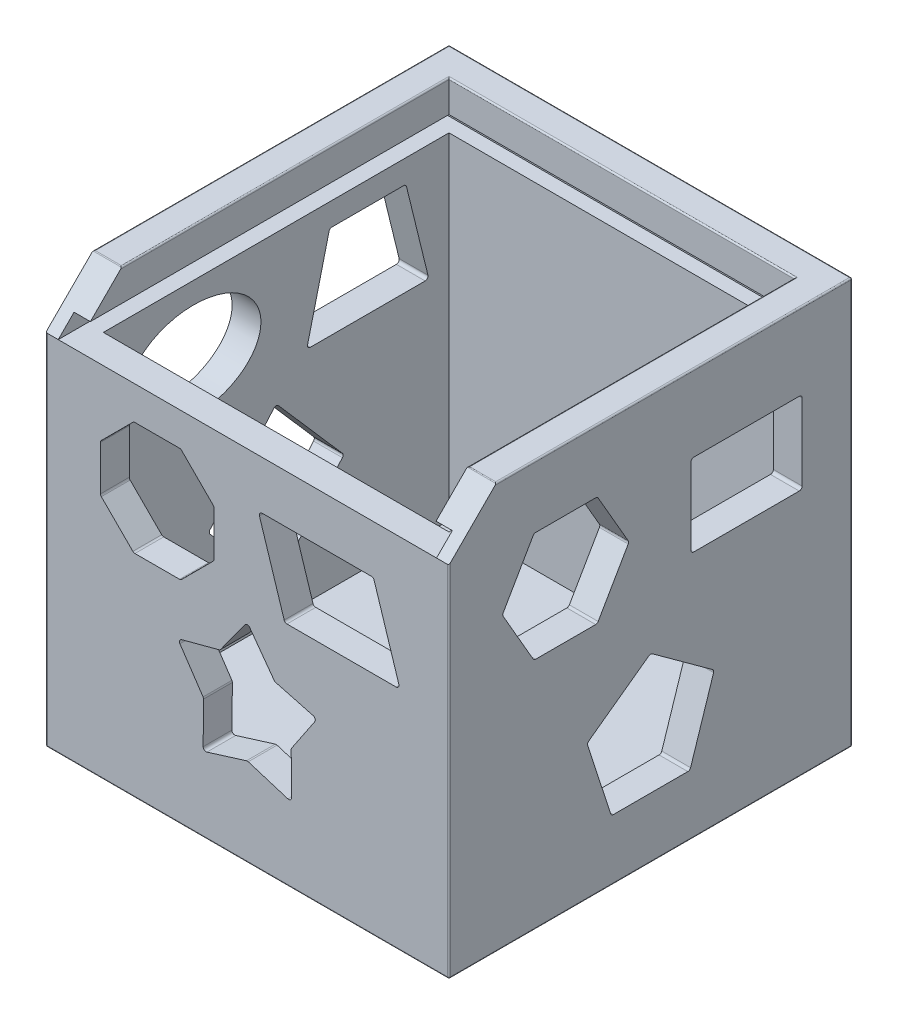
SolidWorks part; units mm, degrees
ref_plane "Front Plane" through (0, 0, 0) normal (0, 0, 1) x (1, 0, 0)
ref_plane "Top Plane" through (0, 0, 0) normal (0, 1, 0) x (1, 0, 0)
ref_plane "Right Plane" through (0, 0, 0) normal (1, 0, 0) x (0, 0, -1)
sketch "Sketch2" plane through (0, 0, 0) normal (0, 1, 0) x (1, 0, 0)
  line L0 (0, 0) -> (96.4229, 0) construction
  line L1 (-70, 70) -> (70, 70)
  line L2 (-70, 70) -> (-70, -70)
  line L3 (-70, -70) -> (70, -70)
  line L4 (70, 70) -> (70, -70)
  line L5 (0, 0) -> (0, 66.2411) construction
  dimension "D1" = 140
  dimension "D2" = 140
extrude "Boss-Extrude1" add sketch "Sketch2" along normal blind 141
sketch "Sketch3" plane through (0, 141, 0) normal (0, 1, 0) x (1, 0, 0)
  line L0 (0, 0) -> (0, 34.3646) construction
  line L1 (-60, 60) -> (60, 60)
  line L2 (-60, 60) -> (-60, -60)
  line L3 (-60, -60) -> (60, -60)
  line L4 (60, 60) -> (60, -60)
  line L5 (0, 0) -> (41.296, 0) construction
  line L6 (-70, 70) -> (-70, -70) construction
  line L7 (70, 70) -> (-70, 70) construction
  dimension "D1" = 10
  dimension "D2" = 10
extrude "Cut-Extrude1" cut sketch "Sketch3" against normal offset from surface (133 mm away) 8 up to face at (0, 0, 0)
sketch "Sketch4" plane through (0, 0, 70) normal (0, 0, 1) x (1, 0, 0)
  line L0 (0, 0) -> (0, 102.2053) construction
  line L1 (-65.6643, 130) -> (65.6643, 130)
  line L2 (-65.6643, 130) -> (-65.6643, 124.5)
  line L3 (-65.6643, 124.5) -> (65.6643, 124.5)
  line L4 (65.6643, 130) -> (65.6643, 124.5)
  line L5 (-70, 141) -> (70, 141) construction
  dimension "D1" = 11
  dimension "D2" = 5.5
extrude "Cut-Extrude2" cut sketch "Sketch4" against normal offset from surface (135 mm away) 5 up to face at (0, 70.5, -70)
sketch "Sketch5" plane through (-70, 0, 0) normal (-1, 0, 0) x (0, 0, 1)
  line L0 (53.5, 141) -> (70, 124.5)
  line L1 (-70, 141) -> (70, 141) construction
  line L2 (70, 141) -> (70, 0) construction
  line L3 (70, 124.5) -> (70, 141)
  line L4 (70, 141) -> (53.5, 141)
  dimension "D1" = 16.5
  dimension "D2" = 16.5
extrude "Cut-Extrude3" cut sketch "Sketch5" against normal through all
sketch "Sketch6" plane through (0, 0, 70) normal (0, 0, 1) x (1, 0, 0)
  line L0 (0, 0) -> (0, 54.0681) construction
  line L1 (-11.6, 85.4542) -> (-11.6, 100.9458)
  line L2 (-11.8929, 101.6529) -> (-22.8471, 112.6071)
  line L3 (-23.5542, 112.9) -> (-39.0458, 112.9)
  line L4 (-39.7529, 112.6071) -> (-50.7071, 101.6529)
  line L5 (-51, 100.9458) -> (-51, 85.4542)
  line L6 (-50.7071, 84.7471) -> (-39.7529, 73.7929)
  line L7 (-39.0458, 73.5) -> (-23.5542, 73.5)
  line L8 (-22.8471, 73.7929) -> (-11.8929, 84.7471)
  line L9 (-15.3591, 27.2492) -> (-15.2085, 41.6454)
  line L15 (0.8079, 71.1757) -> (9.2914, 59.5436)
  line L16 (14.0624, 26.2838) -> (0.2968, 30.5619)
  line L17 (-22.842, 55.7041) -> (-9.842, 59.1665)
  line L18 (23.4148, 54.1803) -> (15.3782, 42.2134)
  line L19 (-9.2914, 59.5436) -> (-0.8079, 71.1757)
  line L20 (9.842, 59.1665) -> (22.842, 55.7041)
  line L21 (-0.2968, 30.5619) -> (-14.0624, 26.2838)
  line L22 (-15.3782, 42.2134) -> (-23.4148, 54.1803)
  line L23 (15.2085, 41.6454) -> (15.3591, 27.2492)
  line L24 (0, 30.6541) -> (0, 72.2835) construction
  line L25 (0, 46.5335) -> (47.7455, 46.5335) construction
  line L26 (-24.196, 55.3435) -> (24.196, 55.3435) construction
  line L27 (-15.3734, 25.8763) -> (15.3734, 25.8763) construction
  line L28 (4.1927, 106.397) -> (12.7784, 79.397)
  line L29 (13.7314, 78.7) -> (51.6327, 78.7)
  line L30 (52.5857, 80.003) -> (44, 107.003)
  line L31 (43.047, 107.7) -> (5.1457, 107.7)
  line L32 (-70, 124.5) -> (-70, 0) construction
  line L33 (65.6643, 124.5) -> (-65.6643, 124.5) construction
  line L34 (70, 124.5) -> (70, 0) construction
  line L37 (-31.3, 93.2) -> (27.5657, 93.2) construction
  line L38 (-70, 0) -> (70, 0) construction
  circle A0 centre (-31.3, 93.2) radius 19.7 construction
  circle A1 centre (0, 46.5335) radius 15.8794 construction
  circle A2 centre (0, 46.5335) radius 25.75 construction
  arc A3 (12.7784, 79.397) -> (13.7314, 78.7) centre (13.7314, 79.7) ccw
  arc A4 (51.6327, 78.7) -> (52.5857, 80.003) centre (51.6327, 79.7) ccw
  arc A5 (44, 107.003) -> (43.047, 107.7) centre (43.047, 106.7) ccw
  arc A6 (4.1927, 106.397) -> (5.1457, 107.7) centre (5.1457, 106.7) cw
  arc A7 (-50.7071, 101.6529) -> (-51, 100.9458) centre (-50, 100.9458) ccw
  arc A8 (-51, 85.4542) -> (-50.7071, 84.7471) centre (-50, 85.4542) ccw
  arc A9 (-39.7529, 73.7929) -> (-39.0458, 73.5) centre (-39.0458, 74.5) ccw
  arc A10 (-23.5542, 73.5) -> (-22.8471, 73.7929) centre (-23.5542, 74.5) ccw
  arc A11 (-11.6, 85.4542) -> (-11.8929, 84.7471) centre (-12.6, 85.4542) cw
  arc A12 (-11.6, 100.9458) -> (-11.8929, 101.6529) centre (-12.6, 100.9458) ccw
  arc A13 (-22.8471, 112.6071) -> (-23.5542, 112.9) centre (-23.5542, 111.9) ccw
  arc A14 (-39.0458, 112.9) -> (-39.7529, 112.6071) centre (-39.0458, 111.9) ccw
  arc A15 (-9.2914, 59.5436) -> (-9.842, 59.1665) centre (-10.0994, 60.1329) cw
  arc A16 (-23.4148, 54.1803) -> (-22.842, 55.7041) centre (-22.5847, 54.7378) cw
  arc A17 (-15.2085, 41.6454) -> (-15.3782, 42.2134) centre (-16.2084, 41.6559) ccw
  arc A18 (-15.3591, 27.2492) -> (-14.0624, 26.2838) centre (-14.3591, 27.2387) ccw
  arc A19 (-0.2968, 30.5619) -> (0.2968, 30.5619) centre (0, 29.607) cw
  arc A20 (14.0624, 26.2838) -> (15.3591, 27.2492) centre (14.3591, 27.2387) ccw
  arc A21 (15.3782, 42.2134) -> (15.2085, 41.6454) centre (16.2084, 41.6559) ccw
  arc A22 (22.842, 55.7041) -> (23.4148, 54.1803) centre (22.5847, 54.7378) cw
  arc A23 (9.842, 59.1665) -> (9.2914, 59.5436) centre (10.0994, 60.1329) cw
  arc A24 (0.8079, 71.1757) -> (-0.8079, 71.1757) centre (0, 70.5864) ccw
  point P40 (53, 78.7)
  point P44 (43.7784, 107.7)
  point P47 (3.7784, 107.7)
  point P71 (-9.5, 59.2576)
  point P77 (-15.2052, 41.9558)
  point P89 (15.2052, 41.9558)
  point P95 (9.5, 59.2576)
  dimension "D1" = 51.5
  dimension "D2" = 32.4168
  dimension "D7" = 1
  dimension "D13" = 1
  dimension "D14" = 1
  dimension "D3" = 40
  dimension "D4" = 29
  dimension "D5" = 17
  dimension "D6" = 16.8
  dimension "D8" = 39.4
  dimension "D9" = 19
  dimension "D10" = 30.6541
  dimension "D11" = 13
  dimension "D12" = 19
  dimension "D15" = 26
extrude "Cut-Extrude4" cut sketch "Sketch6" against normal up to next
sketch "Sketch7" plane through (-70, 0, 0) normal (-1, 0, 0) x (0, 0, 1)
  line L0 (0, 0) -> (0, 78.6985) construction
  line L1 (-70, 0) -> (70, 0) construction
  line L2 (-51.725, 84.1) -> (-11.875, 84.1)
  line L3 (0.7535, 19.8637) -> (22.9821, 45.3426)
  line L4 (22.9821, 46.6574) -> (0.7535, 72.1363)
  line L5 (-0.7535, 72.1363) -> (-22.9821, 46.6574)
  line L6 (-22.9821, 45.3426) -> (-0.7535, 19.8637)
  line L7 (-10.9038, 85.3383) -> (-18.3631, 115.7383)
  line L8 (-19.3343, 116.5) -> (-44.2657, 116.5)
  line L9 (-45.2369, 115.7383) -> (-52.6962, 85.3383)
  line L10 (70, 124.5) -> (70, 0) construction
  line L11 (-70, 141) -> (53.5, 141) construction
  line L12 (-70, 141) -> (-70, 0) construction
  line L13 (-74.584, 100.3) -> (99.8511, 100.3) construction
  line L14 (23.5556, 46) -> (-34.2941, 46) construction
  arc A0 (0.7535, 72.1363) -> (-0.7535, 72.1363) centre (0, 71.4789) ccw
  arc A1 (-51.725, 84.1) -> (-52.6962, 85.3383) centre (-51.725, 85.1) cw
  arc A2 (-11.875, 84.1) -> (-10.9038, 85.3383) centre (-11.875, 85.1) ccw
  arc A3 (-18.3631, 115.7383) -> (-19.3343, 116.5) centre (-19.3343, 115.5) ccw
  arc A4 (-44.2657, 116.5) -> (-45.2369, 115.7383) centre (-44.2657, 115.5) ccw
  arc A5 (-22.9821, 46.6574) -> (-22.9821, 45.3426) centre (-22.2286, 46) ccw
  arc A6 (0.7535, 19.8637) -> (-0.7535, 19.8637) centre (0, 20.5211) cw
  arc A7 (22.9821, 45.3426) -> (22.9821, 46.6574) centre (22.2286, 46) ccw
  ellipse E0 centre (28.65, 100.3) end of major axis (5.3, 100.3) minor radius 16.8
  point P31 (0, 73)
  point P35 (-53, 84.1)
  point P38 (-10.6, 84.1)
  point P41 (-18.55, 116.5)
  point P44 (-45.05, 116.5)
  point P47 (-23.5556, 46)
  point P50 (0, 19)
  dimension "D5" = 1
  dimension "D13" = 1
  dimension "D1" = 19
  dimension "D2" = 35.5
  dimension "D3" = 54
  dimension "D4" = 18
  dimension "D6" = 46.7
  dimension "D7" = 33.6
  dimension "D8" = 42.4
  dimension "D9" = 26.5
  dimension "D10" = 24.5
  dimension "D11" = 17
  dimension "D12" = 32.4
extrude "Cut-Extrude5" cut sketch "Sketch7" against normal up to next
sketch "Sketch9" plane through (70, 0, 0) normal (1, 0, 0) x (0, 0, -1)
  line L0 (0, 0) -> (0, 106.5208) construction
  line L1 (-12.9201, 21) -> (12.9201, 21)
  line L2 (13.8711, 21.691) -> (21.8562, 46.2664)
  line L3 (21.4929, 47.3845) -> (0.5878, 62.5729)
  line L4 (-0.5878, 62.5729) -> (-21.4929, 47.3845)
  line L5 (-21.8562, 46.2664) -> (-13.8711, 21.691)
  line L7 (-70, 0) -> (70, 0) construction
  line L15 (-53.5, 141) -> (70, 141) construction
  line L16 (-56.2003, 100.25) -> (34.8244, 100.25) construction
  line L17 (15, 114.5) -> (51.6, 114.5)
  line L18 (14, 113.5) -> (14, 87)
  line L19 (15, 86) -> (51.6, 86)
  line L20 (52.6, 113.5) -> (52.6, 87)
  line L21 (70, 141) -> (70, 0) construction
  line L22 (-40.7887, 118.8026) -> (-51.2113, 100.75)
  line L23 (-51.2113, 99.75) -> (-40.7887, 81.6974)
  line L24 (-39.9226, 81.1974) -> (-19.0774, 81.1974)
  line L25 (-18.2113, 81.6974) -> (-7.7887, 99.75)
  line L26 (-7.7887, 100.75) -> (-18.2113, 118.8026)
  line L27 (-19.0774, 119.3026) -> (-39.9226, 119.3026)
  circle A0 centre (0, 39.783) radius 18.783 construction
  circle A1 centre (-29.5, 100.25) radius 19.0526 construction
  arc A2 (21.8562, 46.2664) -> (21.4929, 47.3845) centre (20.9051, 46.5755) ccw
  arc A3 (12.9201, 21) -> (13.8711, 21.691) centre (12.9201, 22) ccw
  arc A4 (-12.9201, 21) -> (-13.8711, 21.691) centre (-12.9201, 22) cw
  arc A5 (-21.4929, 47.3845) -> (-21.8562, 46.2664) centre (-20.9051, 46.5755) ccw
  arc A6 (0.5878, 62.5729) -> (-0.5878, 62.5729) centre (0, 61.7639) ccw
  arc A7 (-7.7887, 99.75) -> (-7.7887, 100.75) centre (-8.6547, 100.25) ccw
  arc A8 (-19.0774, 81.1974) -> (-18.2113, 81.6974) centre (-19.0774, 82.1974) ccw
  arc A9 (-40.7887, 81.6974) -> (-39.9226, 81.1974) centre (-39.9226, 82.1974) ccw
  arc A10 (-51.2113, 100.75) -> (-51.2113, 99.75) centre (-50.3453, 100.25) ccw
  arc A11 (-40.7887, 118.8026) -> (-39.9226, 119.3026) centre (-39.9226, 118.3026) cw
  arc A12 (-18.2113, 118.8026) -> (-19.0774, 119.3026) centre (-19.0774, 118.3026) ccw
  arc A13 (51.6, 86) -> (52.6, 87) centre (51.6, 87) ccw
  arc A14 (14, 87) -> (15, 86) centre (15, 87) ccw
  arc A15 (51.6, 114.5) -> (52.6, 113.5) centre (51.6, 113.5) cw
  arc A16 (15, 114.5) -> (14, 113.5) centre (15, 113.5) ccw
  point P46 (0, 63)
  point P49 (-7.5, 100.25)
  point P56 (-51.5, 100.25)
  point P67 (52.6, 114.5)
  point P70 (14, 114.5)
  dimension "D9" = 1
  dimension "D1" = 21
  dimension "D2" = 42
  dimension "D3" = 28.5
  dimension "D4" = 21.5
  dimension "D5" = 44
  dimension "D6" = 17.4
  dimension "D7" = 38.6
  dimension "D8" = 26.5
extrude "Cut-Extrude6" cut sketch "Sketch9" against normal up to next
fillet "Fillet2" radius 0.5 8 edges at (60, 141, -3.25) (0, 141, -60) (-60, 141, -3.25) (-65, 141, 53.5) (-70, 141, -8.25) (0, 141, -70) (70, 141, -8.25) (65, 141, 53.5)
fillet "Fillet6" radius 0.5 6 edges at (69.8536, 140.8536, -69.8536) (-69.8536, 140.8536, -69.8536) (-70, 62.25, 70) (70, 62.25, 70) (70, 70.25, -70) (-70, 70.25, -70)
sketch "Sketch10" plane through (0, 0, -60) normal (0, 0, 1) x (1, 0, 0)
  line L0 (-60, 130) -> (-60, 140.5) construction
  line L1 (-60, 140.5) -> (60, 140.5)
  line L2 (-60, 140.5) -> (-60, 130)
  line L3 (-60, 130) -> (60, 130)
  line L4 (60, 140.5) -> (60, 130)
  line L6 (60, 130) -> (60, 140.5) construction
  line L7 (60, 140.5) -> (-60, 140.5) construction
  line L8 (-60, 130) -> (60, 130) construction
  point P4 (-60, 135.25)
extrude "Cut-Extrude7" cut sketch "Sketch10" along normal blind 131 contours L2 L1 L4 L3
fillet "Fillet7" radius 0.5 8 edges at (70, 0, 0) (69.8536, 0, -69.8536) (0, 0, -70) (-69.8536, 0, -69.8536) (-70, 0, 0) (-69.8536, 0, 69.8536) (0, 0, 70) (69.8536, 0, 69.8536)
